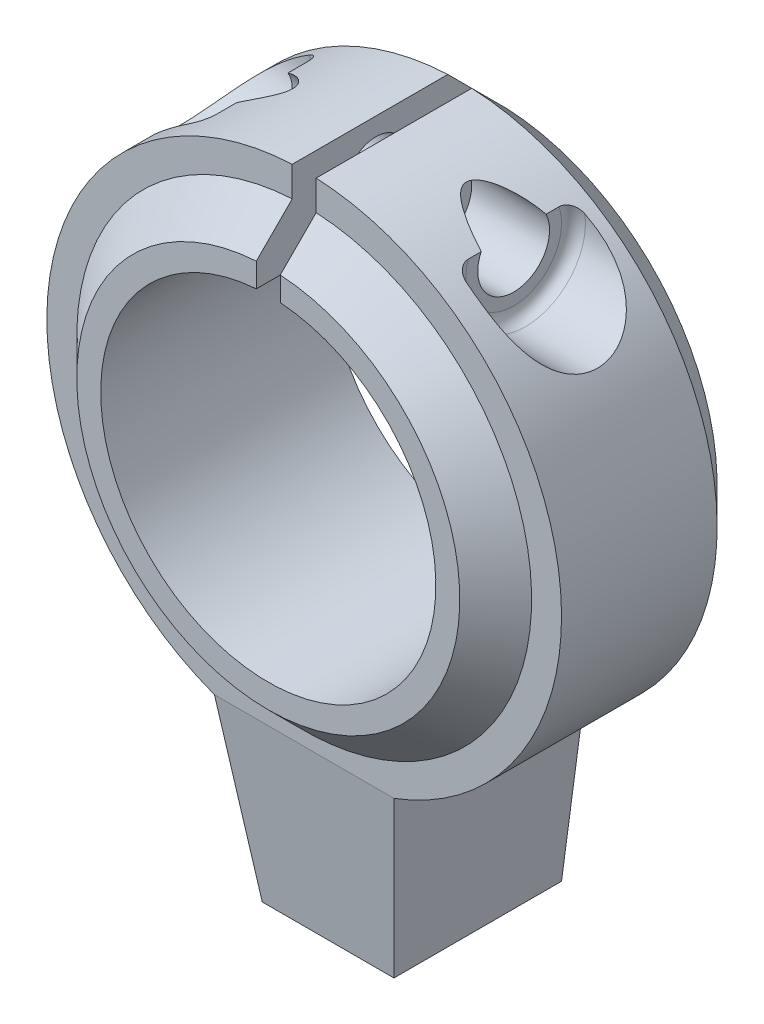
SolidWorks part; units mm, degrees
ref_plane "Front Plane" through (0, 0, 0) normal (0, 0, 1) x (1, 0, 0)
ref_plane "Top Plane" through (0, 0, 0) normal (0, 1, 0) x (1, 0, 0)
ref_plane "Right Plane" through (0, 0, 0) normal (1, 0, 0) x (0, 0, -1)
sketch "Sketch1" plane through (0, 0, 0) normal (0, 0, 1) x (1, 0, 0)
  line L0 (-16.7192, 17.9567) -> (-16.7192, 25.4692)
  line L2 (-23.2192, -16.1569) -> (-8.2192, -16.1569)
  line L3 (-23.2192, -16.1569) -> (-23.2192, -31.1569)
  line L4 (-23.2192, -31.1569) -> (-8.2192, -31.1569)
  line L5 (-8.2192, -16.1569) -> (-8.2192, -31.1569)
  line L9 (-16.7192, 25.4692) -> (-14.7192, 25.4692)
  line L10 (-14.7192, 25.4692) -> (-14.7192, 17.9567)
  circle A0 centre (-15.7192, 3.9925) radius 14
  circle A1 centre (-15.7192, 3.9925) radius 21.5
  dimension "D1" = 28
  dimension "D4" = 43
  dimension "D2" = 15
  dimension "D3" = 15
  dimension "D8" = 2
  dimension "D9" = 1
extrude "Boss-Extrude1" add sketch "Sketch1" along normal blind 16 contours A0 L0 L3 L10 | L3 L4 L5 L2 region at (-25.6664, -6.6925, 0)
sketch "Sketch2" plane through (0, -31.1569, 0) normal (0, -1, 0) x (1, 0, 0)
  line L0 (-23.2192, 0) -> (-8.2192, 0) construction
  circle A0 centre (-15.7192, 8.5) radius 3.05
  dimension "D1" = 6.1
  dimension "D2" = 8.5
extrude "Cut-Extrude1" cut sketch "Sketch2" against normal blind 15
sketch "Sketch3" plane through (0, 0, 16) normal (0, 0, 1) x (1, 0, 0)
  line L0 (-16.7192, 19.9612) -> (-16.7192, 17.9567)
  line L1 (-14.7192, 17.9567) -> (-14.7192, 19.9612)
  line L2 (-14.7192, 25.4692) -> (-14.7192, 17.9567) construction
  line L3 (-16.7192, 17.9567) -> (-16.7192, 25.4692) construction
  circle A0 centre (-15.7192, 3.9925) radius 16
  circle A1 centre (-15.7192, 3.9925) radius 12.25
  line M4 (-14.7192, 25.4692) -> (-14.7192, 17.9567)
  arc M5 (-14.7192, 17.9567) -> (-16.7192, 17.9567) centre (-15.7192, 3.9925) cw
  line M6 (-16.7192, 17.9567) -> (-16.7192, 25.4692)
  dimension "D1" = 32
extrude "Boss-Extrude2" add sketch "Sketch3" along normal blind 3 contours A0 M6 M4 M5 region at (-17.1715, 18.959, 16)
chamfer "Chamfer4" distance 3 angle 45 3 edges at (-15.7192, -12.0075, 16) (5.5234, 7.3096, 0) (-36.9618, 7.3096, 0)
chamfer "Chamfer6" distance 15 distance2 2 3 edges at (-8.2192, -31.1569, 8) (-15.7192, -31.1569, 16) (-23.2192, -31.1569, 8) first distance on face at (-8.2192, -21.1856, 6.7) first distance on face at (-15.7192, -3.803, 16) first distance on face at (-23.2192, -21.8332, 7.3)
sketch "Sketch4" plane through (-14.7192, 0, 0) normal (-1, 0, 0) x (0, 0, 1)
  line L0 (0, 22.4654) -> (0, 17.9567) construction
  line L2 (16, 25.4692) -> (3, 25.4692) construction
  circle A0 centre (9, 21.4692) radius 1.5
  dimension "D1" = 3
  dimension "D2" = 9
  dimension "D3" = 4
extrude "Cut-Extrude2" cut sketch "Sketch4" against normal blind 25 and the other way blind 29
ref_plane "Plane1" through (-37.2192, 0, 0) normal (-1, 0, 0) x (0, 0, 1)
sketch "Sketch5" plane through (-37.2192, 0, 0) normal (-1, 0, 0) x (0, 0, 1)
  circle A0 centre (9, 21.4692) radius 2.5
  circle A1 centre (9, 21.4692) radius 5
  dimension "D1" = 5
  dimension "D2" = 10
extrude "Cut-Extrude3" cut sketch "Sketch5" against normal up to surface (22.5 mm away) contours A0 region at (-37.2192, 21.4692, 9) up to face at (-14.7192, 21.4692, 7.5)
ref_plane "Plane2" through (5.7808, 0, 0) normal (1, 0, 0) x (0, 0, -1)
sketch "Sketch6" plane through (5.7808, 0, 0) normal (1, 0, 0) x (0, 0, -1)
  circle A0 centre (-9, 21.4692) radius 3
  circle A1 centre (-9, 21.4692) radius 5
  dimension "D1" = 6
  dimension "D2" = 10
extrude "Cut-Extrude4" cut sketch "Sketch6" against normal offset from surface (17.5 mm away) 5 contours A0 region at (5.7808, 21.4692, 9) up to face at (-16.7192, 18.9692, 9)
extrude "Cut-Extrude5" cut sketch "Sketch5<3>" against normal blind 11
sketch "Sketch5<3>" plane through (-37.2192, 0, 0) normal (-1, 0, 0) x (0, 0, 1) same geometry as "Sketch5"
extrude "Cut-Extrude6" cut sketch "Sketch6<3>" against normal blind 11
sketch "Sketch6<3>" plane through (5.7808, 0, 0) normal (1, 0, 0) x (0, 0, -1) same geometry as "Sketch6"
fillet "Fillet1" radius 1 2 edges at (-26.2192, 16.4692, 9) (-5.2192, 16.4692, 9)
sketch "Sketch7" plane through (0, 0, 0) normal (0, 0, -1) x (1, 0, 0)
  line L1 (-21.2192, 31.1569) -> (-10.2192, 31.1569) construction
  circle A0 centre (-15.7192, 24.1569) radius 2.25
  dimension "D1" = 4.5
  dimension "D2" = 7
  dimension "D3" = 5.5
extrude "Cut-Extrude7" cut sketch "Sketch7" against normal up to surface (5.45 mm away) up to face at (-15.7192, -16.1569, 5.45)
